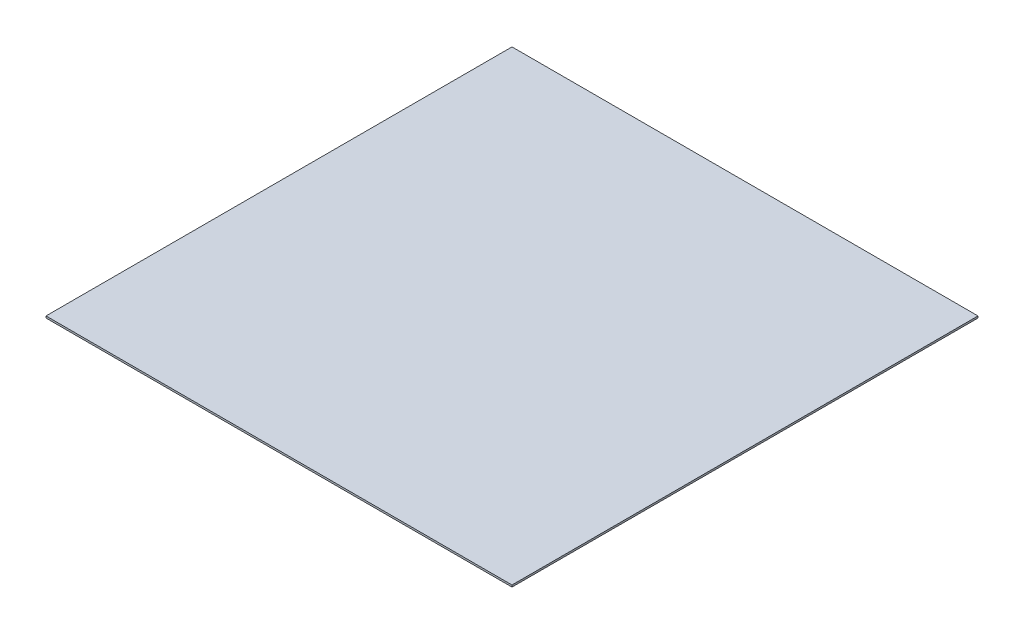
SolidWorks part; units mm, degrees
ref_plane "Front Plane" through (0, 0, 0) normal (0, 0, 1) x (1, 0, 0)
ref_plane "Top Plane" through (0, 0, 0) normal (0, 1, 0) x (1, 0, 0)
ref_plane "Right Plane" through (0, 0, 0) normal (1, 0, 0) x (0, 0, -1)
sketch "Sketch1" plane through (0, 0, 0) normal (0, 1, 0) x (1, 0, 0)
  circle A0 centre (0, 0) radius 75
extrude "Boss-Extrude1" add sketch "Sketch1" along normal blind 10
sketch "Sketch2" plane through (0, 0, 0) normal (0, -1, 0) x (1, 0, 0)
  circle A0 centre (0, 0) radius 45
  circle A1 centre (0, 0) radius 40
  dimension "D1" = 90
  dimension "D2" = 5
extrude "Boss-Extrude2" add sketch "Sketch2" along normal blind 50
sketch "Sketch5" plane through (0, 10, 0) normal (0, 1, 0) x (1, 0, 0)
  line L1 (37.5, -37.5) -> (-37.5, -37.5)
  line L2 (37.5, -37.5) -> (37.5, 37.5)
  line L3 (37.5, 37.5) -> (-37.5, 37.5)
  line L4 (-37.5, -37.5) -> (-37.5, 37.5)
  line L5 (37.5, -37.5) -> (-37.5, 37.5) construction
  line L6 (37.5, 37.5) -> (-37.5, -37.5) construction
  point P0 (0, 0)
  dimension "D1" = 75
  dimension "D2" = 75
extrude "Boss-Extrude3" add sketch "Sketch5" along normal blind 50
sketch "Sketch6" plane through (0, 0, 37.5) normal (0, 0, 1) x (1, 0, 0)
  line L0 (20, 60) -> (37.5, 10)
  line L1 (0, 10) -> (0, 60) construction
  line L2 (-37.5, 60) -> (37.5, 60) construction
  line L3 (20, 60) -> (-20, 60)
  line L4 (-20, 60) -> (-37.5, 10)
  line L5 (-37.5, 10) -> (-42.6786, 10)
  line L6 (75, 10) -> (-75, 10) construction
  line L7 (-42.6786, 10) -> (-42.6786, 63.0346)
  line L8 (-42.6786, 63.0346) -> (43.0697, 63.0346)
  line L9 (43.0697, 63.0346) -> (43.0697, 10)
  line L10 (43.0697, 10) -> (37.5, 10)
  line L11 (-12.9052, 50) -> (-26.9052, 10)
  line L12 (12.9052, 50) -> (26.9052, 10)
  line L13 (12.9052, 50) -> (-12.9052, 50)
  line L14 (-37.5, 10) -> (37.5, 10) construction
  line L15 (10.5614, 56.6965) -> (28.0614, 6.6965) construction
  line L16 (-10.5614, 56.6965) -> (-28.0614, 6.6965) construction
  line L17 (20, 50) -> (-20, 50) construction
  line L18 (-26.9052, 10) -> (26.9052, 10)
extrude "Cut-Extrude2" cut sketch "Sketch6" against normal blind 103
sketch "Sketch7" plane through (0, 0, 0) normal (1, 0, 0) x (0, 0, -1)
  line L0 (-37.5, 10) -> (37.5, 10) construction
  line L1 (0, 10) -> (0, 60) construction
  line L2 (37.5, 60) -> (-37.5, 60) construction
  line L3 (20, 60) -> (-20, 60)
  line L4 (-20, 60) -> (-37.5, 10)
  line L5 (20, 60) -> (37.5, 10)
  line L6 (-37.5, 10) -> (-47.693, 10)
  line L7 (75, 10) -> (-75, 10) construction
  line L8 (-47.693, 10) -> (-47.693, 63.7646)
  line L9 (-47.693, 63.7646) -> (47.4497, 63.7646)
  line L10 (47.4497, 63.7646) -> (47.4497, 10)
  line L11 (47.4497, 10) -> (37.5, 10)
  dimension "D1" = 20
extrude "Cut-Extrude3" cut sketch "Sketch7" against normal blind 103 and the other way blind 103
sketch "Sketch9" plane through (0, 0, 0) normal (1, 0, 0) x (0, 0, -1)
  line L0 (-37.5, 10) -> (37.5, 10) construction
  line L3 (-10, 10) -> (-10, 60)
  line L4 (10, 10) -> (10, 60)
  line L5 (-10, 60) -> (10, 60)
  line L6 (-10, 10) -> (10, 10)
extrude "Cut-Extrude4" cut sketch "Sketch9" against normal blind 103 and the other way blind 103
sketch "Sketch10" plane through (0, 10, 0) normal (0, 1, 0) x (1, 0, 0)
  circle A0 centre (0, 0) radius 5
extrude "Cut-Extrude5" cut sketch "Sketch10" against normal blind 103
sketch "Sketch11" plane through (0, 10, 0) normal (0, 1, 0) x (1, 0, 0)
  line L0 (0, 0) -> (-60, 0) construction
  circle A0 centre (-60, 0) radius 5
  circle A2 centre (30, 51.9615) radius 5
  circle A3 centre (30, -51.9615) radius 5
  point P15 (0, 0)
  dimension "D2" = 3
  dimension "D1" = 60
ref_plane "Plane1" through (0, 210, 0) normal (0, 1, 0) x (1, 0, 0)
sketch "Sketch12" plane through (0, 210, 0) normal (0, 1, 0) x (1, 0, 0)
  circle A0 centre (30, -51.9615) radius 5 construction
  circle A1 centre (30, 51.9615) radius 5 construction
  circle A2 centre (-60, 0) radius 5 construction
  circle A3 centre (30, -51.9615) radius 5
  circle A4 centre (30, 51.9615) radius 5
  circle A5 centre (-60, 0) radius 5
sketch3d "3DSketch1"
  line L0 (-60, 10, 0) -> (-60, 210, 0)
sweep "Sweep1" add profiles "Sketch11" path "3DSketch1"
sketch "Sketch13" plane through (0, 210, 0) normal (0, 1, 0) x (1, 0, 0)
  line L1 (-500, -500) -> (500, -500)
  line L2 (-500, -500) -> (-500, 500)
  line L3 (-500, 500) -> (500, 500)
  line L4 (500, -500) -> (500, 500)
  line L5 (-500, -500) -> (500, 500) construction
  line L6 (-500, 500) -> (500, -500) construction
  point P0 (0, 0)
  dimension "D1" = 1000
  dimension "D2" = 1000
extrude "Boss-Extrude4" add sketch "Sketch13" along normal blind 4
sketch "Sketch16" plane through (0, 0, -10) normal (0, 0, 1) x (1, 0, 0)
  line L0 (0, 60) -> (0, 50) construction
  line L1 (20, 60) -> (-20, 60) construction
  line L2 (-12.9052, 50) -> (12.9052, 50) construction
  circle A0 centre (0, 55) radius 15
  dimension "D1" = 30
sketch "Sketch17" plane through (0, 0, 0) normal (1, 0, 0) x (0, 0, -1)
  line L1 (10, 70) -> (10, 40) construction
  line L2 (10, 55) -> (10, 70)
  line L3 (10, 70) -> (-10, 70) construction
  line L4 (-10, 70) -> (-10, 55)
  line L5 (-10, 70) -> (-5, 70)
  line L6 (10, 70) -> (5, 70)
  line L7 (-5, 70) -> (-3.2375, 60.0045)
  line L8 (5, 70) -> (3.2375, 60.0045)
  line L9 (-3.2375, 60.0045) -> (3.2375, 60.0045)
  line L10 (10, 55) -> (-10, 55)
  dimension "D1" = 5
  dimension "D2" = 5
  dimension "D3" = 10
  dimension "D4" = 10
revolve "Revolve2" add sketch "Sketch17" angle 360 about L10
